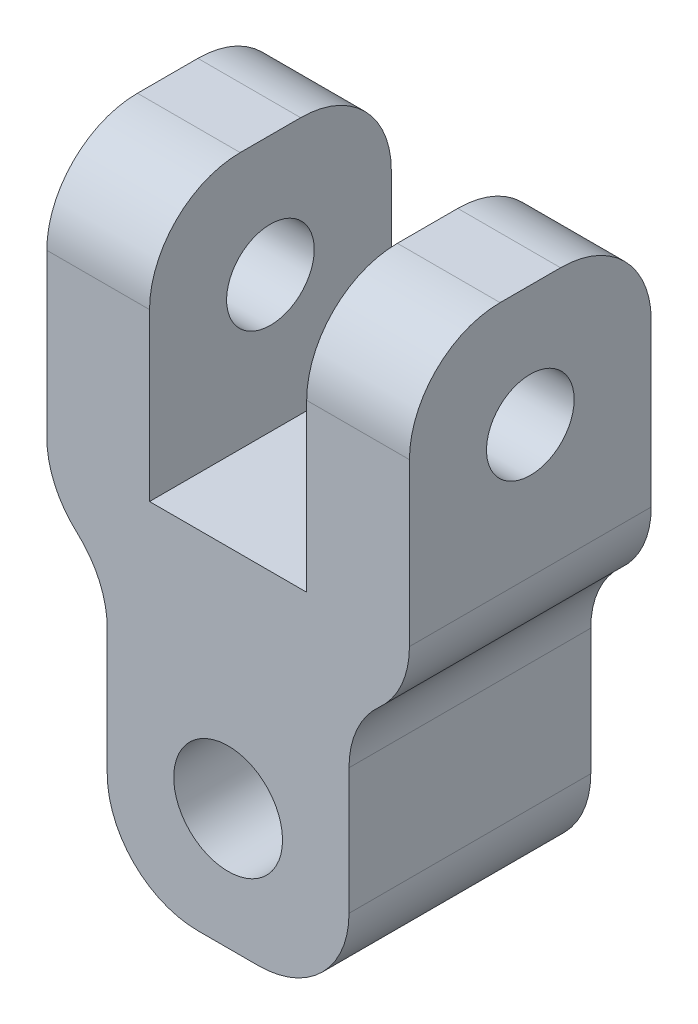
SolidWorks part; units mm, degrees
ref_plane "Front" through (0, 0, 0) normal (0, 0, 1) x (1, 0, 0)
ref_plane "Top" through (0, 0, 0) normal (0, 1, 0) x (1, 0, 0)
ref_plane "Right" through (0, 0, 0) normal (1, 0, 0) x (0, 0, -1)
sketch "草图1" plane through (0, 0, 0) normal (0, 1, 0) x (1, 0, 0)
  line L1 (0, 0) -> (8, 0)
  line L2 (0, 0) -> (0, -8)
  line L3 (0, -8) -> (8, -8)
  line L4 (8, 0) -> (8, -8)
  dimension "D1" = 8
  dimension "D2" = 8
extrude "凸台-拉伸1" add sketch "草图1" along normal blind 20
sketch "草图2" plane through (0, 0, 8) normal (0, 0, 1) x (1, 0, 0)
  line L0 (0, 0) -> (8, 0) construction
  line L1 (8, 20) -> (8, 0) construction
  circle A0 centre (4, 4) radius 1.8
  dimension "D1" = 3.6
  dimension "D2" = 4
  dimension "D3" = 4
extrude "切除-拉伸1" cut sketch "草图2" against normal through all
sketch "草图4" plane through (0, 20, 0) normal (0, 1, 0) x (1, 0, 0)
  line L1 (0, 0) -> (-2, 0)
  line L2 (0, 0) -> (0, -8)
  line L3 (0, -8) -> (-2, -8)
  line L4 (-2, 0) -> (-2, -8)
  line L5 (8, 0) -> (10, 0)
  line L6 (8, 0) -> (8, -8)
  line L7 (8, -8) -> (10, -8)
  line L8 (10, 0) -> (10, -8)
  dimension "D1" = 2
  dimension "D2" = 2
  dimension "D3" = 8
  dimension "D4" = 8
extrude "凸台-拉伸3" add sketch "草图4" against normal blind 10
sketch "草图5" plane through (0, 0, 8) normal (0, 0, 1) x (1, 0, 0)
  line L0 (-2, 20) -> (10, 20) construction
  line L1 (1.4, 20) -> (6.6, 20)
  line L2 (1.4, 20) -> (1.4, 11.5)
  line L3 (1.4, 11.5) -> (6.6, 11.5)
  line L4 (6.6, 20) -> (6.6, 11.5)
  dimension "D1" = 5.2
  dimension "D2" = 3.4
  dimension "D3" = 8.5
extrude "切除-拉伸2" cut sketch "草图5" against normal through all
fillet "圆角1" radius 3 2 edges at (8, 10, 4) (0, 10, 4)
sketch "草图6" plane through (10, 0, 0) normal (1, 0, 0) x (0, 0, -1)
  line L0 (-8, 20) -> (0, 20) construction
  line L1 (0, 10) -> (0, 20) construction
  circle A0 centre (-4, 16) radius 1.45
  dimension "D2" = 4
  dimension "D3" = 4
  dimension "D1" = 2.9
extrude "切除-拉伸3" cut sketch "草图6" against normal through all
fillet "圆角2" radius 3 6 edges at (-2, 10, 4) (10, 10, 4) (-0.3, 20, 0) (-0.3, 20, 8) (0, 0, 4) (8, 0, 4)
equation "\"滑动-垂直孔\" = 0.6"
equation "\"滑动-水平孔\"= 0.3"
equation "\"松动-垂直孔\" = 0.3"
equation "\"松动-水平孔\"= 0.1"
equation "\"正常-垂直孔\" = 0.15"
equation "\"正常-水平孔\"= 0"
equation "\"紧缩-垂直孔\"= 0"
equation "\"紧缩-水平孔\"= - 0.1"
equation "\"D1@草图2\"=\"滑动-垂直孔\"+3"
equation "\"D1@草图6\"=\"紧缩-水平孔\"+3"
